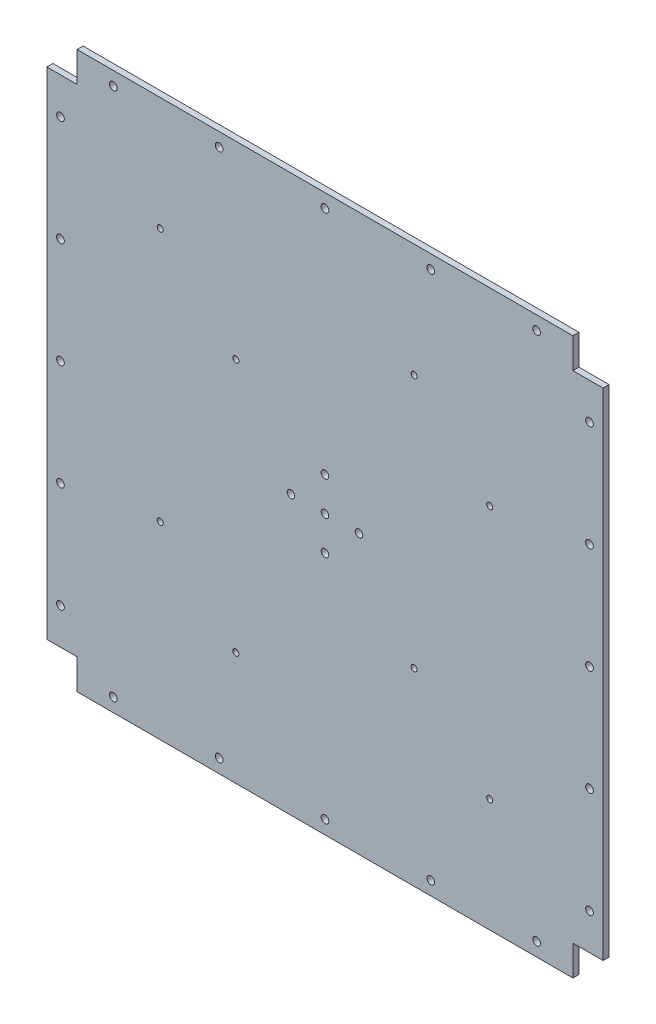
SolidWorks part; units mm, degrees
ref_plane "前视基准面" through (0, 0, 0) normal (0, 0, 1) x (1, 0, 0)
ref_plane "上视基准面" through (0, 0, 0) normal (0, 1, 0) x (1, 0, 0)
ref_plane "右视基准面" through (0, 0, 0) normal (1, 0, 0) x (0, 0, -1)
sketch "草图1" plane through (0, 0, 0) normal (0, 0, 1) x (1, 0, 0)
  line L1 (184, -184) -> (-184, -184)
  line L2 (184, -184) -> (184, 184)
  line L3 (184, 184) -> (-184, 184)
  line L4 (-184, -184) -> (-184, 184)
  line L5 (184, -184) -> (-184, 184) construction
  line L6 (184, 184) -> (-184, -184) construction
  point P0 (0, 0)
  dimension "D1" = 368
  dimension "D2" = 368
extrude "凸台-拉伸1" add sketch "草图1" along normal blind 4
sketch "草图3" plane through (0, 0, 4) normal (0, 0, 1) x (1, 0, 0)
  line L0 (0, -184) -> (0, -175) construction
  line L1 (-184, -184) -> (184, -184) construction
  circle A0 centre (0, -175) radius 2.55
  circle A1 centre (70, -175) radius 2.55
  circle A2 centre (140, -175) radius 2.55
  circle A3 centre (-70, -175) radius 2.55
  circle A4 centre (-140, -175) radius 2.55
  circle A30 centre (-175, 140) radius 2.55
  circle A31 centre (-175, 70) radius 2.55
  circle A32 centre (-175, -70) radius 2.55
  circle A33 centre (-175, -140) radius 2.55
  circle A34 centre (-175, 0) radius 2.55
  circle A35 centre (140, 175) radius 2.55
  circle A36 centre (70, 175) radius 2.55
  circle A37 centre (-70, 175) radius 2.55
  circle A38 centre (-140, 175) radius 2.55
  circle A39 centre (0, 175) radius 2.55
  circle A40 centre (175, -140) radius 2.55
  circle A41 centre (175, -70) radius 2.55
  circle A42 centre (175, 70) radius 2.55
  circle A43 centre (175, 140) radius 2.55
  circle A44 centre (175, 0) radius 2.55
  point P47 (10, -10)
  point P78 (0, 0)
  dimension "D1" = 5.1
  dimension "D2" = 9
  dimension "D3" = 3
  dimension "D4" = 3
  dimension "D6" = 4
extrude "切除-拉伸2" cut sketch "草图3" against normal through all
sketch "草图4" plane through (0, 0, 4) normal (0, 0, 1) x (1, 0, 0)
  line L0 (-164, 184) -> (-164, 164)
  line L1 (-184, -184) -> (-164, -184)
  line L2 (-184, -184) -> (-184, -164)
  line L3 (-184, -164) -> (-164, -164)
  line L4 (-164, -184) -> (-164, -164)
  line L5 (-184, 164) -> (-164, 164)
  line L6 (-184, 184) -> (-164, 184)
  line L7 (-184, 184) -> (-184, 164)
  line L8 (184, 164) -> (164, 164)
  line L9 (164, 184) -> (164, 164)
  line L10 (184, 184) -> (184, 164)
  line L11 (184, 184) -> (164, 184)
  line L12 (164, -184) -> (164, -164)
  line L13 (184, -164) -> (164, -164)
  line L14 (184, -184) -> (164, -184)
  line L15 (184, -184) -> (184, -164)
  point P20 (0, 0)
  dimension "D1" = 20
  dimension "D2" = 20
  dimension "D3" = 4
extrude "切除-拉伸3" cut sketch "草图4" against normal through all contours L0 L5 L7 L6 | L8 L9 L11 L10 | L12 L13 L15 L14 | L2 L1 L4 L3
sketch "草图5" plane through (0, 0, 4) normal (0, 0, 1) x (1, 0, 0)
  line L0 (-184, 0) -> (184, 0) construction
  line L1 (-184, 164) -> (-184, -164) construction
  line L2 (-184, 164) -> (-184, -164) construction
  line L3 (0, 184) -> (0, -184) construction
  line L4 (164, 184) -> (-164, 184) construction
  line L5 (-164, -184) -> (164, -184) construction
  line L6 (-10, 0) -> (-22.5, 0) construction
  line L11 (10, -10) -> (-10, 10) construction
  line L12 (10, 10) -> (-10, -10) construction
  line L13 (0, -10) -> (0, -22.5) construction
  line L14 (10, 0) -> (22.5, 0) construction
  line L15 (0, 10) -> (0, 22.5) construction
  line L16 (-173.9781, 173.9781) -> (0, 0) construction
  line L17 (-184, 0) -> (0, 184) construction
  line L19 (-14.489, 14.489) -> (-159.489, 14.489) construction
  line L20 (-14.489, 14.489) -> (-14.489, 159.489) construction
  line L21 (-14.489, 159.489) -> (-159.489, 159.489) construction
  line L22 (-159.489, 14.489) -> (-159.489, 159.489) construction
  line L23 (-14.489, 14.489) -> (-159.489, 159.489) construction
  line L24 (-14.489, 159.489) -> (-159.489, 14.489) construction
  circle A0 centre (0, 22.5) radius 2.5
  circle A1 centre (22.5, 0) radius 2.5
  circle A2 centre (-22.5, 0) radius 2.5
  circle A3 centre (0, -22.5) radius 2.5
  circle A4 centre (0, 0) radius 2.5
  point P4 (-86.989, 86.989)
  point P12 (0, 0)
  dimension "D7" = 5
  dimension "D8" = 5
  dimension "D9" = 5
  dimension "D10" = 5
  dimension "D11" = 5
  dimension "D1" = 20
  dimension "D2" = 20
  dimension "D3" = 12.5
  dimension "D4" = 12.5
  dimension "D5" = 12.5
  dimension "D6" = 12.5
  dimension "D12" = 145
  dimension "D13" = 145
extrude "切除-拉伸6" cut sketch "草图5" against normal blind 10
sketch "草图6" plane through (0, 0, 4) normal (0, 0, 1) x (1, 0, 0)
  circle A0 centre (-108.99, 108.99) radius 2
  circle A1 centre (-58.99, 58.99) radius 2
  circle A2 centre (58.99, 108.99) radius 2
  circle A3 centre (108.99, 58.99) radius 2
  circle A4 centre (58.99, -58.99) radius 2
  circle A5 centre (108.99, -108.99) radius 2
  circle A6 centre (-58.99, -108.99) radius 2
  circle A7 centre (-108.99, -58.99) radius 2
extrude "切除-拉伸7" cut sketch "草图6" against normal blind 10
